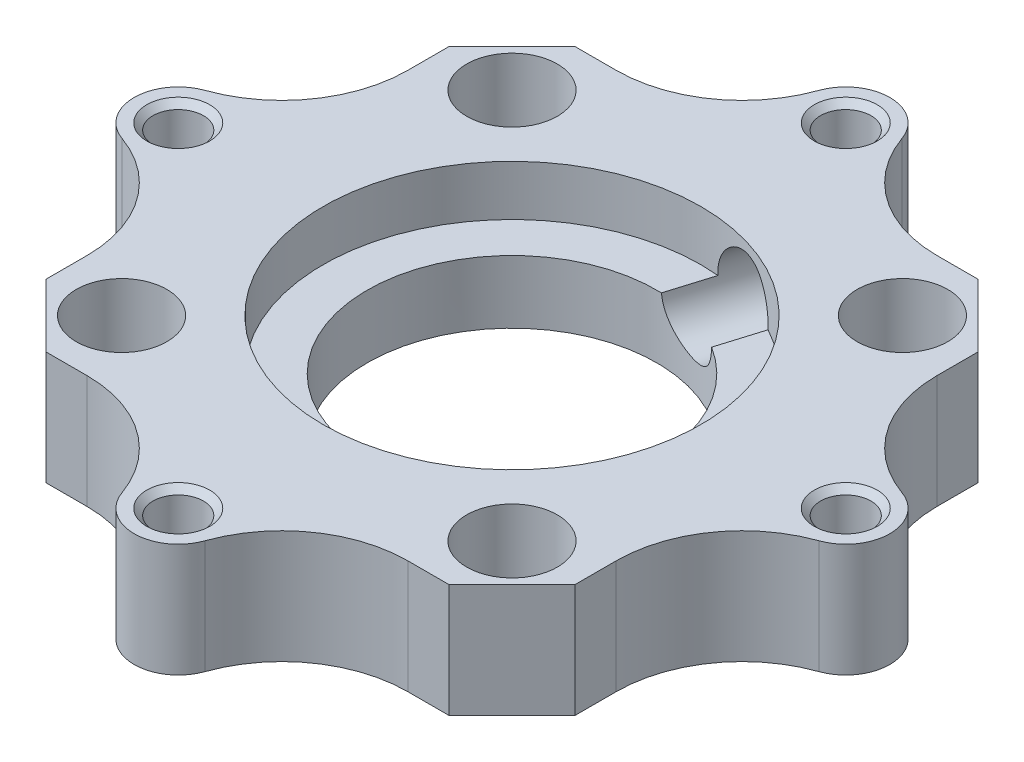
SolidWorks part; units mm, degrees
ref_plane "Front Plane" through (0, 0, 0) normal (0, 0, 1) x (1, 0, 0)
ref_plane "Top Plane" through (0, 0, 0) normal (0, 1, 0) x (1, 0, 0)
ref_plane "Right Plane" through (0, 0, 0) normal (1, 0, 0) x (0, 0, -1)
sketch "Sketch1" plane through (0, 0, 0) normal (0, 1, 0) x (1, 0, 0)
  line L1 (-30, -30) -> (30, -30)
  line L2 (-30, -30) -> (-30, 30)
  line L3 (-30, 30) -> (30, 30)
  line L4 (30, -30) -> (30, 30)
  line L5 (-30, -30) -> (30, 30) construction
  line L6 (-30, 30) -> (30, -30) construction
  circle A0 centre (0, 0) radius 11.5
  point P0 (0, 0)
  dimension "D2" = 23
  dimension "D1" = 60
extrude "Boss-Extrude1" add sketch "Sketch1" along normal blind 5
sketch "Sketch2" plane through (0, 5, 0) normal (0, 1, 0) x (1, 0, 0)
  line L1 (30, -30) -> (-30, -30)
  line L2 (30, -30) -> (30, 30)
  line L3 (30, 30) -> (-30, 30)
  line L4 (-30, -30) -> (-30, 30)
  line L5 (30, -30) -> (-30, 30) construction
  line L6 (30, 30) -> (-30, -30) construction
  circle A0 centre (0, 0) radius 30
  line M1 (30, -30) -> (30, 30)
  line M2 (30, 30) -> (-30, 30)
  line M3 (-30, 30) -> (-30, -30)
  line M4 (-30, -30) -> (30, -30)
extrude "Cut-Extrude1" cut sketch "Sketch2" against normal blind 10 contours A0 L3 M3 | A0 L2 M2 | A0 L1 M1 | A0 L4 M4 region at (23.299, 5, 23.299) region at (-23.299, 5, 23.299) region at (23.299, 5, -23.299) region at (-23.299, 5, -23.299)
sketch "Sketch3" plane through (0, 5, 0) normal (0, 1, 0) x (1, 0, 0)
  line L0 (-12.9544, 12.9544) -> (0, 0) construction
  line L1 (-11.9, -15.5) -> (11.9, -15.5) construction
  line L2 (-15.5, -11.9) -> (-15.5, 11.9) construction
  line L3 (-11.9, 15.5) -> (11.9, 15.5) construction
  line L4 (15.5, -11.9) -> (15.5, 11.9) construction
  line L5 (-12.9544, -12.9544) -> (12.9544, 12.9544) construction
  line L6 (0, 0) -> (12.9544, -12.9544) construction
  line L7 (11.9, 15.5) -> (15.5, 15.5) construction
  line L8 (12.9544, 12.9544) -> (15.5, 15.5) construction
  line L9 (15.5, 11.9) -> (15.5, 15.5) construction
  line L10 (-15.5, 15.5) -> (-11.9, 15.5) construction
  line L11 (-15.5, 15.5) -> (-12.9544, 12.9544) construction
  line L12 (-15.5, 11.9) -> (-15.5, 15.5) construction
  line L13 (-15.5, -15.5) -> (-11.9, -15.5) construction
  line L14 (-15.5, -15.5) -> (-12.9544, -12.9544) construction
  line L15 (-15.5, -15.5) -> (-15.5, -11.9) construction
  line L16 (11.9, -15.5) -> (15.5, -15.5) construction
  line L17 (12.9544, -12.9544) -> (15.5, -15.5) construction
  line L18 (15.5, -15.5) -> (15.5, -11.9) construction
  circle A0 centre (-15.5, 15.5) radius 3.6
  circle A1 centre (15.5, 15.5) radius 3.6
  circle A2 centre (15.5, -15.5) radius 3.6
  circle A3 centre (-15.5, -15.5) radius 3.6
  arc A4 (-15.5, 15.5) -> (-17.828, 12.754) centre (0, 0) ccw construction
  arc A5 (12.754, 17.828) -> (-12.754, 17.828) centre (0, 0) ccw construction
  arc A6 (-17.828, 12.754) -> (-17.828, -12.754) centre (0, 0) ccw construction
  arc A7 (-17.828, -12.754) -> (-15.5, -15.5) centre (0, 0) ccw construction
  arc A8 (-12.754, -17.828) -> (12.754, -17.828) centre (0, 0) ccw construction
  arc A9 (15.5, -15.5) -> (17.828, -12.754) centre (0, 0) ccw construction
  arc A10 (17.828, -12.754) -> (17.828, 12.754) centre (0, 0) ccw construction
  arc A11 (17.828, 12.754) -> (15.5, 15.5) centre (0, 0) ccw construction
  arc A12 (15.5, 15.5) -> (12.754, 17.828) centre (0, 0) ccw construction
  arc A13 (-12.754, 17.828) -> (-15.5, 15.5) centre (0, 0) ccw construction
  arc A14 (-15.5, -15.5) -> (-12.754, -17.828) centre (0, 0) ccw construction
  arc A15 (12.754, -17.828) -> (15.5, -15.5) centre (0, 0) ccw construction
  point P0 (0, 0)
  point P17 (0, 0)
  dimension "D2" = 7.2
  dimension "D1" = 31
  dimension "D3" = 4
extrude "Cut-Extrude2" cut sketch "Sketch3" against normal blind 3
sketch "Sketch4" plane through (0, 2, 0) normal (0, 1, 0) x (1, 0, 0)
  circle A0 centre (-15.5, 15.5) radius 1.6
  circle A1 centre (15.5, 15.5) radius 1.6
  circle A2 centre (15.5, -15.5) radius 1.6
  circle A3 centre (-15.5, -15.5) radius 1.6
  point P12 (0, 0)
  dimension "D1" = 3.2
  dimension "D2" = 4
extrude "Cut-Extrude3" cut sketch "Sketch4" against normal blind 3
sketch "Sketch5" plane through (0, 5, 0) normal (0, 1, 0) x (1, 0, 0)
  line L0 (0, 30) -> (0, -30) construction
  line L1 (-23, 0) -> (23, 0) construction
  line L2 (-30, 0) -> (-23, 0) construction
  arc A0 (-30, 0) -> (-23, 0) centre (-26.5, 0) ccw construction
  arc A1 (-23, 0) -> (-30, 0) centre (-26.5, 0) ccw construction
  circle A2 centre (-26.5, 0) radius 2
  circle A3 centre (0, 26.5) radius 2
  circle A4 centre (26.5, 0) radius 2
  circle A5 centre (0, -26.5) radius 2
  point P5 (0, 0)
  point P6 (0, 0)
  point P19 (0, 0)
  dimension "D2" = 7
  dimension "D3" = 4
  dimension "D1" = 60
  dimension "D4" = 4
extrude "Cut-Extrude4" cut sketch "Sketch5" against normal through all
sketch "Sketch6" plane through (0, 5, 0) normal (0, 1, 0) x (1, 0, 0)
  line L0 (3.5, 21) -> (21, 21)
  line L1 (-26.5, 3.5) -> (-21, 3.5)
  line L2 (-26.5, -3.5) -> (-21, -3.5)
  line L3 (21, 3.5) -> (21, 21)
  line L4 (3.5, 26.5) -> (3.5, 21)
  line L5 (-3.5, 26.5) -> (-3.5, 21)
  line L6 (3.5, -21) -> (21, -21)
  line L7 (-21, -21) -> (-3.5, -21)
  line L8 (-21, -21) -> (-21, -3.5)
  line L9 (-21, 21) -> (-3.5, 21)
  line L10 (21, -21) -> (21, -3.5)
  line L11 (-21, 3.5) -> (-21, 21)
  line L15 (-3.5, -21) -> (-3.5, -26.5)
  line L17 (3.5, -21) -> (3.5, -26.5)
  line L18 (21, -3.5) -> (26.5, -3.5)
  line L20 (21, 3.5) -> (26.5, 3.5)
  arc A0 (-26.5, 3.5) -> (-26.5, -3.5) centre (-26.5, 0) ccw
  arc A1 (26.5, -3.5) -> (26.5, 3.5) centre (26.5, 0) ccw
  arc A2 (3.5, 26.5) -> (-3.5, 26.5) centre (0, 26.5) ccw
  arc A3 (-3.5, -26.5) -> (3.5, -26.5) centre (0, -26.5) ccw
  circle A4 centre (0, 0) radius 30
  point P4 (0, 0)
  point P9 (0, 0)
  point P18 (0, 0)
  circle M23 centre (0, 0) radius 30
  dimension "D1" = 3.5
  dimension "D2" = 3.5
  dimension "D3" = 42
extrude "Cut-Extrude5" cut sketch "Sketch6" against normal through all contours A2 A0 L1 L11 L9 L5 M23 | A2 L4 L0 L3 L20 A1 M23 | A3 L15 L7 L8 L2 A0 M23 | A3 A1 L18 L10 L6 L17 M23 region at (3.9243, 5, -23.75) region at (-2.7749, 5, -29.2749) region at (21.1832, 5, 21.1832) region at (-29.2749, 5, 2.7749)
chamfer "Chamfer1" distance 5 angle 45 4 edges at (-21, 2.5, -21) (-21, 2.5, 21) (21, 2.5, 21) (21, 2.5, -21)
fillet "Fillet1" radius 10 8 edges at (3.5, 2.5, -21) (-3.5, 2.5, -21) (-21, 2.5, -3.5) (-21, 2.5, 3.5) (-3.5, 2.5, 21) (3.5, 2.5, 21) (21, 2.5, 3.5) (21, 2.5, -3.5)
sketch "Sketch7" plane through (0, 5, 0) normal (0, 1, 0) x (1, 0, 0)
  line L12 (-21, -12.7279) -> (-21, -16)
  line L13 (-21, -16) -> (-16, -21)
  line L14 (-16, -21) -> (-12.7279, -21)
  line L15 (12.7279, -21) -> (16, -21)
  line L16 (16, -21) -> (21, -16)
  line L17 (21, -16) -> (21, -12.7279)
  line L18 (21, 12.7279) -> (21, 16)
  line L19 (21, 16) -> (16, 21)
  line L20 (16, 21) -> (12.7279, 21)
  line L21 (-12.7279, 21) -> (-16, 21)
  line L22 (-16, 21) -> (-21, 16)
  line L23 (-21, 16) -> (-21, 12.7279)
  line L24 (-21, -12.7279) -> (-21, -16)
  line L25 (-21, -16) -> (-16, -21)
  line L26 (-16, -21) -> (-12.7279, -21)
  line L27 (12.7279, -21) -> (16, -21)
  line L28 (16, -21) -> (21, -16)
  line L29 (21, -16) -> (21, -12.7279)
  line L30 (21, 12.7279) -> (21, 16)
  line L31 (21, 16) -> (16, 21)
  line L32 (16, 21) -> (12.7279, 21)
  line L33 (-12.7279, 21) -> (-16, 21)
  line L34 (-16, 21) -> (-21, 16)
  line L35 (-21, 16) -> (-21, 12.7279)
  circle A0 centre (-26.5, 0) radius 2
  circle A1 centre (0, 26.5) radius 2
  circle A2 centre (26.5, 0) radius 2
  circle A3 centre (0, -26.5) radius 2
  circle A4 centre (-15.5, 15.5) radius 3.6
  circle A5 centre (15.5, 15.5) radius 3.6
  circle A6 centre (15.5, -15.5) radius 3.6
  circle A7 centre (-15.5, -15.5) radius 3.6
  circle A8 centre (0, 0) radius 11.5
  arc A12 (-3.2998, -27.6667) -> (-12.7279, -21) centre (-12.7279, -31) ccw
  arc A13 (-3.2998, -27.6667) -> (3.2998, -27.6667) centre (0, -26.5) ccw
  arc A14 (12.7279, -21) -> (3.2998, -27.6667) centre (12.7279, -31) ccw
  arc A15 (27.6667, -3.2998) -> (21, -12.7279) centre (31, -12.7279) ccw
  arc A16 (27.6667, -3.2998) -> (27.6667, 3.2998) centre (26.5, 0) ccw
  arc A17 (21, 12.7279) -> (27.6667, 3.2998) centre (31, 12.7279) ccw
  arc A18 (3.2998, 27.6667) -> (12.7279, 21) centre (12.7279, 31) ccw
  arc A19 (3.2998, 27.6667) -> (-3.2998, 27.6667) centre (0, 26.5) ccw
  arc A20 (-12.7279, 21) -> (-3.2998, 27.6667) centre (-12.7279, 31) ccw
  arc A21 (-27.6667, 3.2998) -> (-21, 12.7279) centre (-31, 12.7279) ccw
  arc A22 (-27.6667, 3.2998) -> (-27.6667, -3.2998) centre (-26.5, 0) ccw
  arc A23 (-21, -12.7279) -> (-27.6667, -3.2998) centre (-31, -12.7279) ccw
  arc A24 (-3.2998, -27.6667) -> (-12.7279, -21) centre (-12.7279, -31) ccw
  arc A25 (-3.2998, -27.6667) -> (3.2998, -27.6667) centre (0, -26.5) ccw
  arc A26 (12.7279, -21) -> (3.2998, -27.6667) centre (12.7279, -31) ccw
  arc A27 (27.6667, -3.2998) -> (21, -12.7279) centre (31, -12.7279) ccw
  arc A28 (27.6667, -3.2998) -> (27.6667, 3.2998) centre (26.5, 0) ccw
  arc A29 (21, 12.7279) -> (27.6667, 3.2998) centre (31, 12.7279) ccw
  arc A30 (3.2998, 27.6667) -> (12.7279, 21) centre (12.7279, 31) ccw
  arc A31 (3.2998, 27.6667) -> (-3.2998, 27.6667) centre (0, 26.5) ccw
  arc A32 (-12.7279, 21) -> (-3.2998, 27.6667) centre (-12.7279, 31) ccw
  arc A33 (-27.6667, 3.2998) -> (-21, 12.7279) centre (-31, 12.7279) ccw
  arc A34 (-27.6667, 3.2998) -> (-27.6667, -3.2998) centre (-26.5, 0) ccw
  arc A35 (-21, -12.7279) -> (-27.6667, -3.2998) centre (-31, -12.7279) ccw
  point P39 (0, 0)
  point P54 (0, 0)
  dimension "D1" = 0
  dimension "D2" = 4
  dimension "D3" = 4
extrude "Boss-Extrude2" add sketch "Sketch7" along normal blind 4
sketch "Sketch8" plane through (0, 9, 0) normal (0, 1, 0) x (1, 0, 0)
  circle A0 centre (0, 0) radius 15
  dimension "D1" = 30
extrude "Cut-Extrude6" cut sketch "Sketch8" against normal blind 4
sketch "Sketch9" plane through (0, 9, 0) normal (0, 1, 0) x (1, 0, 0)
  line L0 (0, 0) -> (30, 0) construction
  line L1 (0, 0) -> (0, 30) construction
  line L2 (0, 30) -> (6.9544, 22.835) construction
  line L3 (6.9544, 22.835) -> (0, 0) construction
  arc A0 (27.6667, -3.2998) -> (27.6667, 3.2998) centre (26.5, 0) ccw construction
  arc A1 (3.2998, 27.6667) -> (-3.2998, 27.6667) centre (0, 26.5) ccw construction
  arc A2 (3.2998, 27.6667) -> (12.7279, 21) centre (12.7279, 31) ccw construction
ref_plane "Plane1" through (6.8067, 0, -22.3499) normal (0.2913, 0, -0.9566) x (-0.9566, 0, -0.2913)
sketch "Sketch10" plane through (6.8067, 0, -22.3499) normal (0.2913, 0, -0.9566) x (-0.9566, 0, -0.2913)
  line L0 (0, 8.9079) -> (0, 0) construction
  circle A0 centre (0, 5.2353) radius 3
  dimension "D1" = 6
extrude "Cut-Extrude7" cut sketch "Sketch10" against normal blind 16 and the other way blind 10
chamfer "Chamfer2" distance 0.5 angle 45 4 edges at (-26.5, 9, 2) (0, 9, -24.5) (26.5, 9, 2) (0, 9, 28.5)
sketch "Sketch11" plane through (0, 0, 0) normal (0, -1, 0) x (1, 0, 0)
  point P0 (0, 0)
